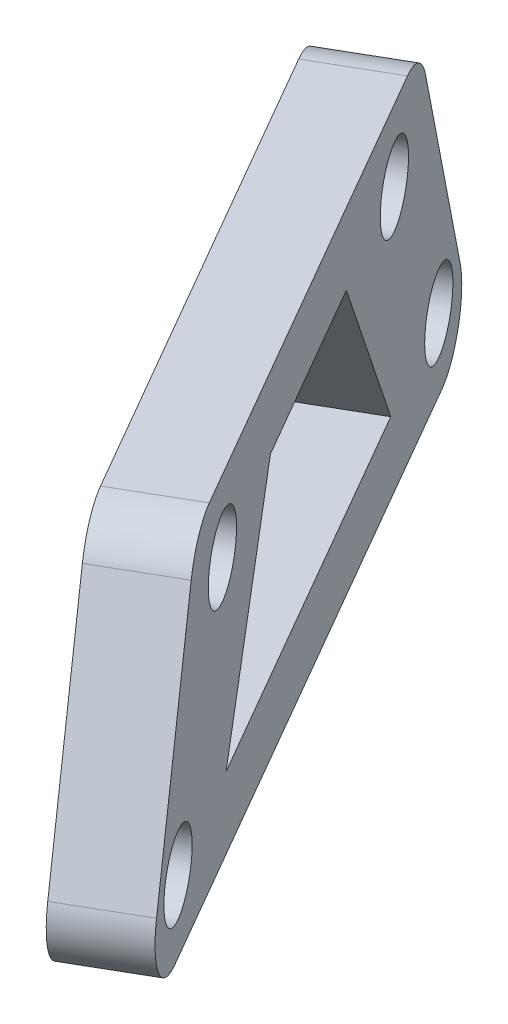
SolidWorks part; units mm, degrees
ref_plane "Front Plane" through (0, 0, 0) normal (0, 0, 1) x (1, 0, 0)
ref_plane "Top Plane" through (0, 0, 0) normal (0, 1, 0) x (1, 0, 0)
ref_plane "Right Plane" through (0, 0, 0) normal (1, 0, 0) x (0, 0, -1)
sketch "Sketch1" plane through (-13.1956, 0, 7.6185) normal (-0.866, 0, 0.5) x (0.5, 0, 0.866)
  line L0 (-25.1342, 118.0559) -> (-17.3608, 136.7988)
  line L1 (-17.3608, 136.7988) -> (16.8858, 136.7988)
  line L2 (16.8858, 136.7988) -> (24.6592, 118.0559)
  line L3 (24.6592, 118.0559) -> (-25.1342, 118.0559)
  line L4 (-13.3608, 132.7988) -> (12.8858, 132.7988) construction
  line L5 (-12.8047, 122.0559) -> (-6.0314, 132.7988)
  line L6 (-17.6728, 114.3347) -> (-12.1063, 123.1637) construction
  line L7 (-10.8995, 125.0777) -> (-5.333, 133.9066) construction
  line L8 (-6.0314, 132.7988) -> (5.5564, 132.7988)
  line L9 (10.4245, 125.0777) -> (4.858, 133.9066) construction
  line L10 (5.5564, 132.7988) -> (12.3297, 122.0559)
  line L11 (17.1978, 114.3347) -> (11.6313, 123.1637) construction
  line L12 (12.3297, 122.0559) -> (-12.8047, 122.0559)
  circle A0 centre (-13.3608, 132.7988) radius 2.15
  circle A1 centre (12.8858, 132.7988) radius 2.15
  circle A2 centre (19.6592, 122.0559) radius 2.15
  circle A3 centre (-20.1342, 122.0559) radius 2.15
  point P0 (-20.1342, 122.0559)
  point P2 (19.6592, 122.0559)
  point P4 (12.8858, 132.7988)
  point P6 (-13.3608, 132.7988)
  point P20 (-0.2375, 136.7988)
  point P21 (-0.2375, 132.7988)
  dimension "D1" = 4.3
  dimension "D2" = 4
  dimension "D3" = 4
  dimension "D4" = 5
  dimension "D5" = 4
  dimension "D6" = 5
  dimension "D7" = 4
  dimension "D8" = 4
extrude "Boss-Extrude1" add sketch "Sketch1" against normal blind 4.45
fillet "Fillet1" radius 3 4 edges at (1.0609, 118.0559, 27.8614) (-2.8258, 136.7988, 21.1295) (-19.9491, 136.7988, -8.5289) (-23.8358, 118.0559, -15.2609)
